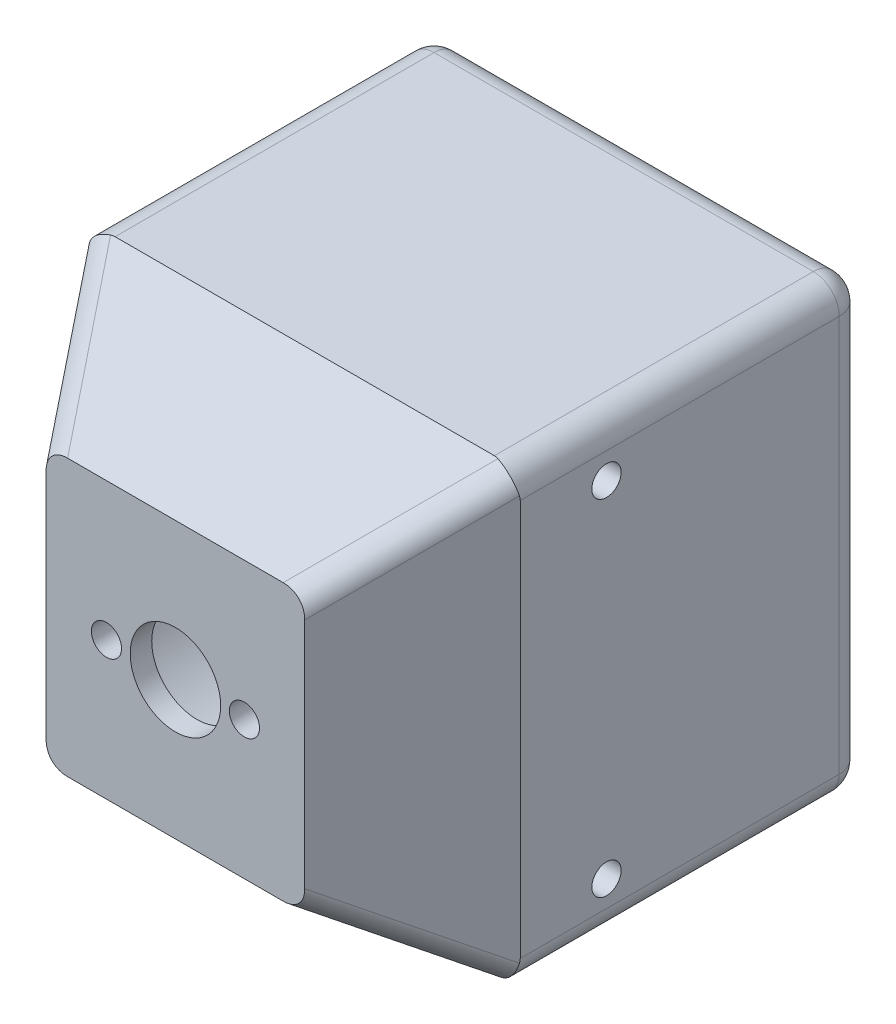
SolidWorks part; units mm, degrees
ref_plane "Front Plane" through (0, 0, 0) normal (0, 0, 1) x (1, 0, 0)
ref_plane "Top Plane" through (0, 0, 0) normal (0, 1, 0) x (1, 0, 0)
ref_plane "Right Plane" through (0, 0, 0) normal (1, 0, 0) x (0, 0, -1)
sketch "Sketch1" plane through (0, 0, 0) normal (0, 0, 1) x (1, 0, 0)
  line L1 (-25, 26) -> (25, 26)
  line L2 (-25, 26) -> (-25, -26)
  line L3 (-25, -26) -> (25, -26)
  line L4 (25, 26) -> (25, -26)
  line L5 (-25, 26) -> (25, -26) construction
  line L6 (-25, -26) -> (25, 26) construction
  point P0 (0, 0)
  dimension "D1" = 50
  dimension "D2" = 52
extrude "Boss-Extrude1" add sketch "Sketch1" along normal blind 82.5
sketch "Sketch2" plane through (0, 0, 0) normal (0, 0, -1) x (-1, 0, 0)
  circle A0 centre (0, 0) radius 15
  dimension "D1" = 30
extrude "Cut-Extrude1" cut sketch "Sketch2" against normal blind 80
sketch "Sketch3" plane through (0, 0, 82.5) normal (0, 0, 1) x (1, 0, 0)
  line L0 (0, 0) -> (50000, 0) construction
  line L1 (0, 0) -> (0, -50000) construction
  circle A0 centre (0, 0) radius 5.25
  circle A1 centre (-8, 0) radius 1.75
  circle A2 centre (8, 0) radius 1.75
  dimension "D1" = 10.5
  dimension "D2" = 3.5
  dimension "D3" = 8
extrude "Cut-Extrude2" cut sketch "Sketch3" against normal through all
sketch "Sketch4" plane through (25, 0, 0) normal (1, 0, 0) x (0, 0, -1)
  line L2 (-82.5, 26) -> (0, 26) construction
  line L3 (-82.5, -26) -> (-82.5, 26) construction
  line L4 (0, 0) -> (50000, 0) construction
  line L5 (0, -26) -> (0, 26) construction
  circle A0 centre (-57.5, 20) radius 1.7
  circle A2 centre (-57.5, -20) radius 1.7
  point P10 (0, 0)
  dimension "D1" = 3.4
  dimension "D2" = 25
  dimension "D3" = 6
extrude "Cut-Extrude4" cut sketch "Sketch4" against normal through all
sketch "Sketch6" plane through (25, 0, 0) normal (1, 0, 0) x (0, 0, -1)
  line L0 (-82.5, 26) -> (0, 26) construction
  line L1 (0, -26) -> (-27.5, -26)
  line L2 (0, -26) -> (0, 26)
  line L3 (0, 26) -> (-27.5, 26)
  line L4 (-27.5, -26) -> (-27.5, 26)
  dimension "D1" = 27.5
extrude "Cut-Extrude5" cut sketch "Sketch6" against normal through all
sketch "Sketch9" plane through (25, 0, 0) normal (1, 0, 0) x (0, 0, -1)
  line L0 (-82.5, 26) -> (-82.5, 16)
  line L1 (-82.5, -26) -> (-82.5, 26) construction
  line L2 (-82.5, 16) -> (-67.5, 26)
  line L3 (-82.5, 26) -> (-27.5, 26) construction
  line L4 (-67.5, 26) -> (-82.5, 26)
  line L5 (-82.5, 0) -> (49917.5, 0) construction
  line L6 (-82.5, -16) -> (-67.5, -26)
  line L7 (-82.5, -26) -> (-82.5, -16)
  line L8 (-67.5, -26) -> (-82.5, -26)
  point P10 (-82.5, 0)
  dimension "D1" = 10
  dimension "D2" = 15
extrude "Cut-Extrude6" cut sketch "Sketch9" against normal through all
sketch "Sketch10" plane through (0, -26, 0) normal (0, -1, 0) x (1, 0, 0)
  line L0 (15, 82.5) -> (25, 67.5)
  line L1 (-25, 82.5) -> (25, 82.5) construction
  line L2 (25, 67.5) -> (25, 82.5)
  line L3 (25, 82.5) -> (15, 82.5)
  line L4 (0, 67.5) -> (0, -49932.5) construction
  line L5 (-25, 67.5) -> (25, 67.5) construction
  line L6 (-25, 67.5) -> (-25, 82.5)
  line L7 (-15, 82.5) -> (-25, 67.5)
  line L8 (-25, 82.5) -> (-15, 82.5)
  point P11 (0, 67.5)
  dimension "D1" = 10
extrude "Cut-Extrude7" cut sketch "Sketch10" against normal through all
fillet "Fillet1" radius 3 13 edges at (-20, 21, 75) (-20, -21, 75) (20, -21, 75) (25, -26, 47.5) (-25, -26, 47.5) (-25, 26, 47.5) (25, 26, 47.5) (0, -15, 27.5) (0, 26, 27.5) (-25, 0, 27.5) (0, -26, 27.5) (25, 0, 27.5) (20, 21, 75)
